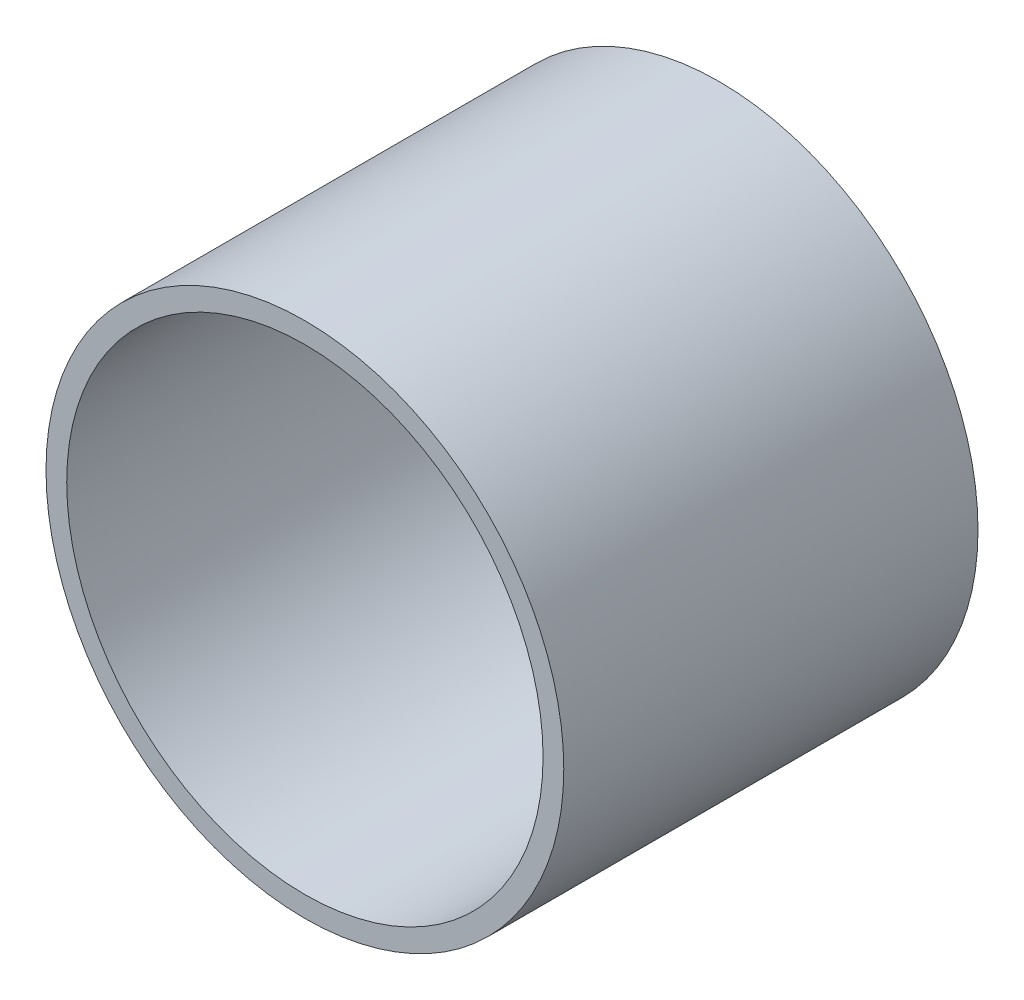
SolidWorks part; units mm, degrees
ref_plane "Front" through (0, 0, 0) normal (0, 0, 1) x (1, 0, 0)
ref_plane "Top" through (0, 0, 0) normal (0, 1, 0) x (1, 0, 0)
ref_plane "Right" through (0, 0, 0) normal (1, 0, 0) x (0, 0, -1)
sketch "Sketch1" plane through (0, 0, 0) normal (0, 0, 1) x (1, 0, 0)
  circle A0 centre (0, 0) radius 3.9688
  dimension "D1" = 7.9375
extrude "Extrude1" add sketch "Sketch1" along normal blind 6.35
shell "Shell1" thickness 0.3175 removed face at (3.9688, 0, 0) removed face at (3.9688, 0, 6.35)
